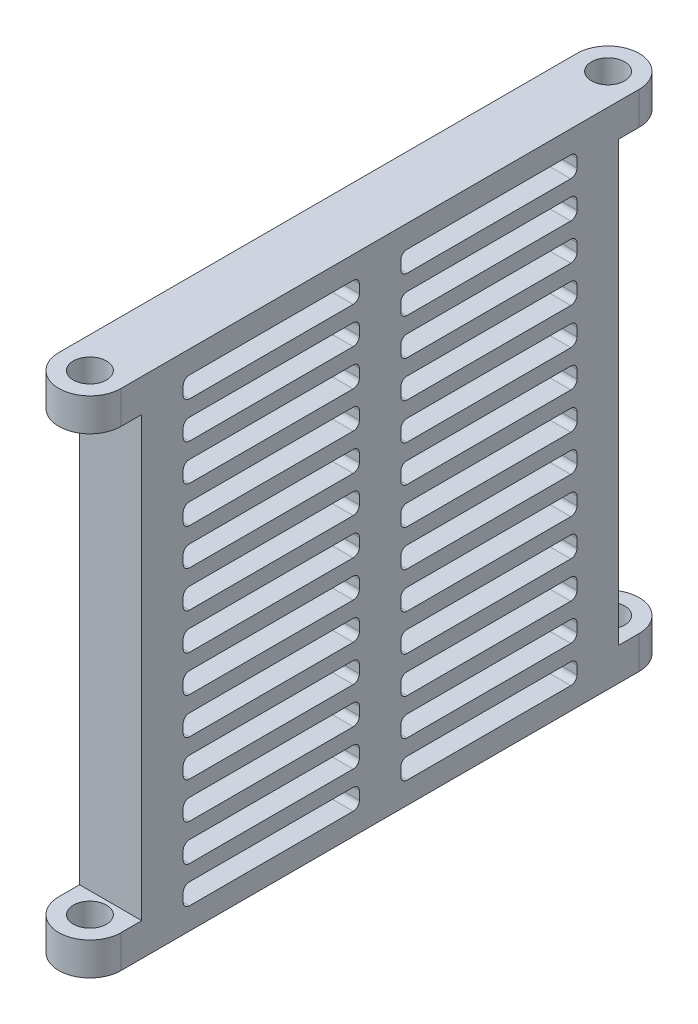
SolidWorks part; units mm, degrees
ref_plane "Front Plane" through (0, 0, 0) normal (0, 0, 1) x (1, 0, 0)
ref_plane "Top Plane" through (0, 0, 0) normal (0, 1, 0) x (1, 0, 0)
ref_plane "Right Plane" through (0, 0, 0) normal (1, 0, 0) x (0, 0, -1)
sketch "Sketch2" plane through (0, 0, 0) normal (0, 1, 0) x (1, 0, 0)
  line L0 (-3, 0) -> (-3, -50)
  line L1 (3, -50) -> (3, 0)
  arc A0 (3, 0) -> (-3, 0) centre (0, 0) ccw
  arc A1 (-3, -50) -> (3, -50) centre (0, -50) ccw
  circle A2 centre (0, 0) radius 1.6
  circle A3 centre (0, -50) radius 1.6
  dimension "D1" = 3.2
  dimension "D2" = 3
  dimension "D3" = 50
extrude "Boss-Extrude1" add sketch "Sketch2" along normal blind 3.175
sketch "Sketch3" plane through (0, 3.175, 0) normal (0, 1, 0) x (1, 0, 0)
  line L0 (-3, 0) -> (-3, -50) construction
  line L1 (-3, -2) -> (3, -2)
  line L2 (-3, -2) -> (-3, -48)
  line L3 (-3, -48) -> (3, -48)
  line L4 (3, -2) -> (3, -48)
  line L5 (3, -50) -> (3, 0) construction
  circle A0 centre (0, -50) radius 1.6 construction
  point P9 (0, -48)
  dimension "D1" = 2
  dimension "D2" = 2
extrude "Boss-Extrude2" add sketch "Sketch3" along normal blind 42.3
ref_plane "Plane1" through (0, 24.325, 0) normal (0, 1, 0) x (1, 0, 0)
mirror "Mirror2" about plane through (0, 24.325, 0) normal (0, 1, 0) of "Boss-Extrude1"
sketch "Sketch4" plane through (3, 0, 0) normal (1, 0, 0) x (0, 0, -1)
  line L0 (-2, 45.475) -> (-48, 45.475) construction
  line L3 (-2, 3.175) -> (-48, 3.175) construction
  line L11 (-25, 48.65) -> (-25, 0) construction
  line L12 (-50, 48.65) -> (0, 48.65) construction
  line L24 (-50, 0) -> (0, 0) construction
  line L25 (-2, 45.475) -> (-2, 3.175) construction
  line L30 (-6.6, 46.475) -> (-22.4, 46.475)
  line L39 (-6, 45.875) -> (-6, 45.075)
  line L40 (-6.6, 44.475) -> (-22.4, 44.475)
  line L41 (-23, 45.875) -> (-23, 45.075)
  line L46 (-6, 46.475) -> (-23, 44.475) construction
  line L47 (-6, 44.475) -> (-23, 46.475) construction
  line L64 (-6.6, 42.945) -> (-22.4, 42.945)
  line L69 (-6, 42.345) -> (-6, 41.545)
  line L70 (-6.6, 40.945) -> (-22.4, 40.945)
  line L71 (-23, 42.345) -> (-23, 41.545)
  line L72 (-2, 41.945) -> (-48, 41.945) construction
  line L73 (-6, 42.945) -> (-23, 40.945) construction
  line L74 (-6, 40.945) -> (-23, 42.945) construction
  line L75 (-6.6, 39.415) -> (-22.4, 39.415)
  line L76 (-6, 38.815) -> (-6, 38.015)
  line L77 (-6.6, 37.415) -> (-22.4, 37.415)
  line L78 (-23, 38.815) -> (-23, 38.015)
  line L79 (-2, 38.415) -> (-48, 38.415) construction
  line L132 (-6, 39.415) -> (-23, 37.415) construction
  line L133 (-6, 37.415) -> (-23, 39.415) construction
  line L134 (-6.6, 35.885) -> (-22.4, 35.885)
  line L135 (-6, 35.285) -> (-6, 34.485)
  line L136 (-6.6, 33.885) -> (-22.4, 33.885)
  line L137 (-23, 35.285) -> (-23, 34.485)
  line L138 (-2, 34.885) -> (-48, 34.885) construction
  line L139 (-6, 35.885) -> (-23, 33.885) construction
  line L140 (-6, 33.885) -> (-23, 35.885) construction
  line L141 (-6.6, 32.355) -> (-22.4, 32.355)
  line L142 (-6, 31.755) -> (-6, 30.955)
  line L143 (-6.6, 30.355) -> (-22.4, 30.355)
  line L144 (-23, 31.755) -> (-23, 30.955)
  line L145 (-2, 31.355) -> (-48, 31.355) construction
  line L146 (-6, 32.355) -> (-23, 30.355) construction
  line L147 (-6, 30.355) -> (-23, 32.355) construction
  line L148 (-6.6, 28.825) -> (-22.4, 28.825)
  line L149 (-6, 28.225) -> (-6, 27.425)
  line L201 (-6.6, 26.825) -> (-22.4, 26.825)
  line L202 (-23, 28.225) -> (-23, 27.425)
  line L203 (-2, 27.825) -> (-48, 27.825) construction
  line L204 (-6, 28.825) -> (-23, 26.825) construction
  line L205 (-6, 26.825) -> (-23, 28.825) construction
  line L206 (-6.6, 25.295) -> (-22.4, 25.295)
  line L207 (-6, 24.695) -> (-6, 23.895)
  line L208 (-6.6, 23.295) -> (-22.4, 23.295)
  line L209 (-23, 24.695) -> (-23, 23.895)
  line L210 (-2, 24.295) -> (-48, 24.295) construction
  line L211 (-6, 25.295) -> (-23, 23.295) construction
  line L212 (-6, 23.295) -> (-23, 25.295) construction
  line L213 (-6.6, 21.765) -> (-22.4, 21.765)
  line L214 (-6, 21.165) -> (-6, 20.365)
  line L215 (-6.6, 19.765) -> (-22.4, 19.765)
  line L216 (-23, 21.165) -> (-23, 20.365)
  line L217 (-2, 20.765) -> (-48, 20.765) construction
  line L218 (-6, 21.765) -> (-23, 19.765) construction
  line L219 (-6, 19.765) -> (-23, 21.765) construction
  line L220 (-6.6, 18.235) -> (-22.4, 18.235)
  line L221 (-6, 17.635) -> (-6, 16.835)
  line L222 (-6.6, 16.235) -> (-22.4, 16.235)
  line L223 (-23, 17.635) -> (-23, 16.835)
  line L224 (-2, 17.235) -> (-48, 17.235) construction
  line L225 (-6, 18.235) -> (-23, 16.235) construction
  line L226 (-6, 16.235) -> (-23, 18.235) construction
  line L227 (-6.6, 14.705) -> (-22.4, 14.705)
  line L228 (-6, 14.105) -> (-6, 13.305)
  line L229 (-6.6, 12.705) -> (-22.4, 12.705)
  line L230 (-23, 14.105) -> (-23, 13.305)
  line L231 (-2, 13.705) -> (-48, 13.705) construction
  line L232 (-6, 14.705) -> (-23, 12.705) construction
  line L233 (-6, 12.705) -> (-23, 14.705) construction
  line L234 (-6.6, 11.175) -> (-22.4, 11.175)
  line L235 (-6, 10.575) -> (-6, 9.775)
  line L236 (-6.6, 9.175) -> (-22.4, 9.175)
  line L237 (-23, 10.575) -> (-23, 9.775)
  line L238 (-2, 10.175) -> (-48, 10.175) construction
  line L239 (-6, 11.175) -> (-23, 9.175) construction
  line L240 (-6, 9.175) -> (-23, 11.175) construction
  line L241 (-6.6, 7.645) -> (-22.4, 7.645)
  line L242 (-6, 7.045) -> (-6, 6.245)
  line L243 (-6.6, 5.645) -> (-22.4, 5.645)
  line L244 (-23, 7.045) -> (-23, 6.245)
  line L245 (-2, 6.645) -> (-48, 6.645) construction
  line L246 (-6, 7.645) -> (-23, 5.645) construction
  line L247 (-6, 5.645) -> (-23, 7.645) construction
  line L248 (-6.6, 4.115) -> (-22.4, 4.115)
  line L249 (-6, 3.515) -> (-6, 2.715)
  line L250 (-6.6, 2.115) -> (-22.4, 2.115)
  line L251 (-23, 3.515) -> (-23, 2.715)
  line L252 (-2, 3.115) -> (-48, 3.115) construction
  line L253 (-6, 4.115) -> (-23, 2.115) construction
  line L254 (-6, 2.115) -> (-23, 4.115) construction
  line L255 (-44, 2.115) -> (-27, 4.115) construction
  line L256 (-44, 4.115) -> (-27, 2.115) construction
  line L257 (-44, 5.645) -> (-27, 7.645) construction
  line L258 (-44, 7.645) -> (-27, 5.645) construction
  line L259 (-44, 9.175) -> (-27, 11.175) construction
  line L260 (-44, 11.175) -> (-27, 9.175) construction
  line L261 (-44, 12.705) -> (-27, 14.705) construction
  line L262 (-44, 14.705) -> (-27, 12.705) construction
  line L263 (-44, 16.235) -> (-27, 18.235) construction
  line L264 (-44, 18.235) -> (-27, 16.235) construction
  line L265 (-44, 19.765) -> (-27, 21.765) construction
  line L266 (-44, 21.765) -> (-27, 19.765) construction
  line L267 (-44, 23.295) -> (-27, 25.295) construction
  line L268 (-44, 25.295) -> (-27, 23.295) construction
  line L269 (-44, 26.825) -> (-27, 28.825) construction
  line L270 (-44, 28.825) -> (-27, 26.825) construction
  line L271 (-44, 30.355) -> (-27, 32.355) construction
  line L272 (-44, 32.355) -> (-27, 30.355) construction
  line L273 (-44, 33.885) -> (-27, 35.885) construction
  line L274 (-44, 35.885) -> (-27, 33.885) construction
  line L275 (-44, 37.415) -> (-27, 39.415) construction
  line L276 (-44, 39.415) -> (-27, 37.415) construction
  line L277 (-44, 40.945) -> (-27, 42.945) construction
  line L278 (-44, 42.945) -> (-27, 40.945) construction
  line L279 (-44, 44.475) -> (-27, 46.475) construction
  line L280 (-44, 46.475) -> (-27, 44.475) construction
  line L281 (-27, 3.515) -> (-27, 2.715)
  line L282 (-43.4, 2.115) -> (-27.6, 2.115)
  line L283 (-44, 3.515) -> (-44, 2.715)
  line L284 (-43.4, 4.115) -> (-27.6, 4.115)
  line L285 (-27, 7.045) -> (-27, 6.245)
  line L286 (-43.4, 5.645) -> (-27.6, 5.645)
  line L287 (-44, 7.045) -> (-44, 6.245)
  line L288 (-43.4, 7.645) -> (-27.6, 7.645)
  line L289 (-27, 10.575) -> (-27, 9.775)
  line L290 (-43.4, 9.175) -> (-27.6, 9.175)
  line L291 (-44, 10.575) -> (-44, 9.775)
  line L292 (-43.4, 11.175) -> (-27.6, 11.175)
  line L293 (-27, 14.105) -> (-27, 13.305)
  line L294 (-43.4, 12.705) -> (-27.6, 12.705)
  line L295 (-44, 14.105) -> (-44, 13.305)
  line L296 (-43.4, 14.705) -> (-27.6, 14.705)
  line L297 (-27, 17.635) -> (-27, 16.835)
  line L298 (-43.4, 16.235) -> (-27.6, 16.235)
  line L299 (-44, 17.635) -> (-44, 16.835)
  line L300 (-43.4, 18.235) -> (-27.6, 18.235)
  line L301 (-27, 21.165) -> (-27, 20.365)
  line L302 (-43.4, 19.765) -> (-27.6, 19.765)
  line L303 (-44, 21.165) -> (-44, 20.365)
  line L304 (-43.4, 21.765) -> (-27.6, 21.765)
  line L305 (-27, 24.695) -> (-27, 23.895)
  line L306 (-43.4, 23.295) -> (-27.6, 23.295)
  line L307 (-44, 24.695) -> (-44, 23.895)
  line L308 (-43.4, 25.295) -> (-27.6, 25.295)
  line L309 (-27, 28.225) -> (-27, 27.425)
  line L310 (-43.4, 26.825) -> (-27.6, 26.825)
  line L311 (-44, 28.225) -> (-44, 27.425)
  line L312 (-43.4, 28.825) -> (-27.6, 28.825)
  line L313 (-27, 31.755) -> (-27, 30.955)
  line L314 (-43.4, 30.355) -> (-27.6, 30.355)
  line L315 (-44, 31.755) -> (-44, 30.955)
  line L316 (-43.4, 32.355) -> (-27.6, 32.355)
  line L317 (-27, 35.285) -> (-27, 34.485)
  line L318 (-43.4, 33.885) -> (-27.6, 33.885)
  line L319 (-44, 35.285) -> (-44, 34.485)
  line L320 (-43.4, 35.885) -> (-27.6, 35.885)
  line L321 (-27, 38.815) -> (-27, 38.015)
  line L322 (-43.4, 37.415) -> (-27.6, 37.415)
  line L323 (-44, 38.815) -> (-44, 38.015)
  line L324 (-43.4, 39.415) -> (-27.6, 39.415)
  line L325 (-27, 42.345) -> (-27, 41.545)
  line L326 (-43.4, 40.945) -> (-27.6, 40.945)
  line L327 (-44, 42.345) -> (-44, 41.545)
  line L328 (-43.4, 42.945) -> (-27.6, 42.945)
  line L329 (-27, 45.875) -> (-27, 45.075)
  line L330 (-43.4, 44.475) -> (-27.6, 44.475)
  line L331 (-44, 45.875) -> (-44, 45.075)
  line L332 (-43.4, 46.475) -> (-27.6, 46.475)
  arc A76 (-22.4, 46.475) -> (-23, 45.875) centre (-22.4, 45.875) ccw
  arc A77 (-22.4, 44.475) -> (-23, 45.075) centre (-22.4, 45.075) cw
  arc A78 (-6.6, 46.475) -> (-6, 45.875) centre (-6.6, 45.875) cw
  arc A79 (-6, 45.075) -> (-6.6, 44.475) centre (-6.6, 45.075) cw
  arc A80 (-22.4, 42.945) -> (-23, 42.345) centre (-22.4, 42.345) ccw
  arc A81 (-22.4, 40.945) -> (-23, 41.545) centre (-22.4, 41.545) cw
  arc A82 (-6.6, 42.945) -> (-6, 42.345) centre (-6.6, 42.345) cw
  arc A83 (-6, 41.545) -> (-6.6, 40.945) centre (-6.6, 41.545) cw
  arc A84 (-22.4, 39.415) -> (-23, 38.815) centre (-22.4, 38.815) ccw
  arc A85 (-22.4, 37.415) -> (-23, 38.015) centre (-22.4, 38.015) cw
  arc A86 (-6.6, 39.415) -> (-6, 38.815) centre (-6.6, 38.815) cw
  arc A87 (-6, 38.015) -> (-6.6, 37.415) centre (-6.6, 38.015) cw
  arc A88 (-22.4, 35.885) -> (-23, 35.285) centre (-22.4, 35.285) ccw
  arc A89 (-22.4, 33.885) -> (-23, 34.485) centre (-22.4, 34.485) cw
  arc A90 (-6.6, 35.885) -> (-6, 35.285) centre (-6.6, 35.285) cw
  arc A91 (-6, 34.485) -> (-6.6, 33.885) centre (-6.6, 34.485) cw
  arc A92 (-22.4, 32.355) -> (-23, 31.755) centre (-22.4, 31.755) ccw
  arc A93 (-22.4, 30.355) -> (-23, 30.955) centre (-22.4, 30.955) cw
  arc A94 (-6.6, 32.355) -> (-6, 31.755) centre (-6.6, 31.755) cw
  arc A95 (-6, 30.955) -> (-6.6, 30.355) centre (-6.6, 30.955) cw
  arc A96 (-22.4, 28.825) -> (-23, 28.225) centre (-22.4, 28.225) ccw
  arc A97 (-22.4, 26.825) -> (-23, 27.425) centre (-22.4, 27.425) cw
  arc A98 (-6.6, 28.825) -> (-6, 28.225) centre (-6.6, 28.225) cw
  arc A99 (-6, 27.425) -> (-6.6, 26.825) centre (-6.6, 27.425) cw
  arc A100 (-22.4, 25.295) -> (-23, 24.695) centre (-22.4, 24.695) ccw
  arc A101 (-22.4, 23.295) -> (-23, 23.895) centre (-22.4, 23.895) cw
  arc A102 (-6.6, 25.295) -> (-6, 24.695) centre (-6.6, 24.695) cw
  arc A103 (-6, 23.895) -> (-6.6, 23.295) centre (-6.6, 23.895) cw
  arc A104 (-22.4, 21.765) -> (-23, 21.165) centre (-22.4, 21.165) ccw
  arc A105 (-22.4, 19.765) -> (-23, 20.365) centre (-22.4, 20.365) cw
  arc A106 (-6.6, 21.765) -> (-6, 21.165) centre (-6.6, 21.165) cw
  arc A107 (-6, 20.365) -> (-6.6, 19.765) centre (-6.6, 20.365) cw
  arc A108 (-22.4, 18.235) -> (-23, 17.635) centre (-22.4, 17.635) ccw
  arc A109 (-22.4, 16.235) -> (-23, 16.835) centre (-22.4, 16.835) cw
  arc A110 (-6.6, 18.235) -> (-6, 17.635) centre (-6.6, 17.635) cw
  arc A111 (-6, 16.835) -> (-6.6, 16.235) centre (-6.6, 16.835) cw
  arc A112 (-22.4, 14.705) -> (-23, 14.105) centre (-22.4, 14.105) ccw
  arc A113 (-22.4, 12.705) -> (-23, 13.305) centre (-22.4, 13.305) cw
  arc A114 (-6.6, 14.705) -> (-6, 14.105) centre (-6.6, 14.105) cw
  arc A115 (-6, 13.305) -> (-6.6, 12.705) centre (-6.6, 13.305) cw
  arc A116 (-22.4, 11.175) -> (-23, 10.575) centre (-22.4, 10.575) ccw
  arc A117 (-22.4, 9.175) -> (-23, 9.775) centre (-22.4, 9.775) cw
  arc A118 (-6.6, 11.175) -> (-6, 10.575) centre (-6.6, 10.575) cw
  arc A119 (-6, 9.775) -> (-6.6, 9.175) centre (-6.6, 9.775) cw
  arc A120 (-22.4, 7.645) -> (-23, 7.045) centre (-22.4, 7.045) ccw
  arc A121 (-22.4, 5.645) -> (-23, 6.245) centre (-22.4, 6.245) cw
  arc A122 (-6.6, 7.645) -> (-6, 7.045) centre (-6.6, 7.045) cw
  arc A123 (-6, 6.245) -> (-6.6, 5.645) centre (-6.6, 6.245) cw
  arc A124 (-22.4, 4.115) -> (-23, 3.515) centre (-22.4, 3.515) ccw
  arc A125 (-22.4, 2.115) -> (-23, 2.715) centre (-22.4, 2.715) cw
  arc A126 (-6.6, 4.115) -> (-6, 3.515) centre (-6.6, 3.515) cw
  arc A127 (-6, 2.715) -> (-6.6, 2.115) centre (-6.6, 2.715) cw
  arc A128 (-44, 2.715) -> (-43.4, 2.115) centre (-43.4, 2.715) ccw
  arc A129 (-43.4, 4.115) -> (-44, 3.515) centre (-43.4, 3.515) ccw
  arc A130 (-27.6, 2.115) -> (-27, 2.715) centre (-27.6, 2.715) ccw
  arc A131 (-27.6, 4.115) -> (-27, 3.515) centre (-27.6, 3.515) cw
  arc A132 (-44, 6.245) -> (-43.4, 5.645) centre (-43.4, 6.245) ccw
  arc A133 (-43.4, 7.645) -> (-44, 7.045) centre (-43.4, 7.045) ccw
  arc A134 (-27.6, 5.645) -> (-27, 6.245) centre (-27.6, 6.245) ccw
  arc A135 (-27.6, 7.645) -> (-27, 7.045) centre (-27.6, 7.045) cw
  arc A136 (-44, 9.775) -> (-43.4, 9.175) centre (-43.4, 9.775) ccw
  arc A137 (-43.4, 11.175) -> (-44, 10.575) centre (-43.4, 10.575) ccw
  arc A138 (-27.6, 9.175) -> (-27, 9.775) centre (-27.6, 9.775) ccw
  arc A139 (-27.6, 11.175) -> (-27, 10.575) centre (-27.6, 10.575) cw
  arc A140 (-44, 13.305) -> (-43.4, 12.705) centre (-43.4, 13.305) ccw
  arc A141 (-43.4, 14.705) -> (-44, 14.105) centre (-43.4, 14.105) ccw
  arc A142 (-27.6, 12.705) -> (-27, 13.305) centre (-27.6, 13.305) ccw
  arc A143 (-27.6, 14.705) -> (-27, 14.105) centre (-27.6, 14.105) cw
  arc A144 (-44, 16.835) -> (-43.4, 16.235) centre (-43.4, 16.835) ccw
  arc A145 (-43.4, 18.235) -> (-44, 17.635) centre (-43.4, 17.635) ccw
  arc A146 (-27.6, 16.235) -> (-27, 16.835) centre (-27.6, 16.835) ccw
  arc A147 (-27.6, 18.235) -> (-27, 17.635) centre (-27.6, 17.635) cw
  arc A148 (-44, 20.365) -> (-43.4, 19.765) centre (-43.4, 20.365) ccw
  arc A149 (-43.4, 21.765) -> (-44, 21.165) centre (-43.4, 21.165) ccw
  arc A150 (-27.6, 19.765) -> (-27, 20.365) centre (-27.6, 20.365) ccw
  arc A151 (-27.6, 21.765) -> (-27, 21.165) centre (-27.6, 21.165) cw
  arc A152 (-44, 23.895) -> (-43.4, 23.295) centre (-43.4, 23.895) ccw
  arc A153 (-43.4, 25.295) -> (-44, 24.695) centre (-43.4, 24.695) ccw
  arc A154 (-27.6, 23.295) -> (-27, 23.895) centre (-27.6, 23.895) ccw
  arc A155 (-27.6, 25.295) -> (-27, 24.695) centre (-27.6, 24.695) cw
  arc A156 (-44, 27.425) -> (-43.4, 26.825) centre (-43.4, 27.425) ccw
  arc A157 (-43.4, 28.825) -> (-44, 28.225) centre (-43.4, 28.225) ccw
  arc A158 (-27.6, 26.825) -> (-27, 27.425) centre (-27.6, 27.425) ccw
  arc A159 (-27.6, 28.825) -> (-27, 28.225) centre (-27.6, 28.225) cw
  arc A160 (-44, 30.955) -> (-43.4, 30.355) centre (-43.4, 30.955) ccw
  arc A161 (-43.4, 32.355) -> (-44, 31.755) centre (-43.4, 31.755) ccw
  arc A162 (-27.6, 30.355) -> (-27, 30.955) centre (-27.6, 30.955) ccw
  arc A163 (-27.6, 32.355) -> (-27, 31.755) centre (-27.6, 31.755) cw
  arc A164 (-44, 34.485) -> (-43.4, 33.885) centre (-43.4, 34.485) ccw
  arc A165 (-43.4, 35.885) -> (-44, 35.285) centre (-43.4, 35.285) ccw
  arc A166 (-27.6, 33.885) -> (-27, 34.485) centre (-27.6, 34.485) ccw
  arc A167 (-27.6, 35.885) -> (-27, 35.285) centre (-27.6, 35.285) cw
  arc A168 (-44, 38.015) -> (-43.4, 37.415) centre (-43.4, 38.015) ccw
  arc A169 (-43.4, 39.415) -> (-44, 38.815) centre (-43.4, 38.815) ccw
  arc A170 (-27.6, 37.415) -> (-27, 38.015) centre (-27.6, 38.015) ccw
  arc A171 (-27.6, 39.415) -> (-27, 38.815) centre (-27.6, 38.815) cw
  arc A172 (-44, 41.545) -> (-43.4, 40.945) centre (-43.4, 41.545) ccw
  arc A173 (-43.4, 42.945) -> (-44, 42.345) centre (-43.4, 42.345) ccw
  arc A174 (-27.6, 40.945) -> (-27, 41.545) centre (-27.6, 41.545) ccw
  arc A175 (-27.6, 42.945) -> (-27, 42.345) centre (-27.6, 42.345) cw
  arc A176 (-44, 45.075) -> (-43.4, 44.475) centre (-43.4, 45.075) ccw
  arc A177 (-43.4, 46.475) -> (-44, 45.875) centre (-43.4, 45.875) ccw
  arc A178 (-27.6, 44.475) -> (-27, 45.075) centre (-27.6, 45.075) ccw
  arc A179 (-27.6, 46.475) -> (-27, 45.875) centre (-27.6, 45.875) cw
  point P10 (-14.5, 45.475)
  point P13 (-14.25, 34.325)
  point P14 (-14.25, 31.825)
  point P15 (-14.25, 29.325)
  point P16 (-14.25, 26.825)
  point P36 (-14.5, 41.945)
  point P55 (-14.5, 38.415)
  point P74 (-14.5, 34.885)
  point P93 (-14.5, 31.355)
  point P112 (-14.5, 27.825)
  point P131 (-14.5, 24.295)
  point P150 (-14.5, 20.765)
  point P169 (-14.5, 17.235)
  point P188 (-14.5, 13.705)
  point P207 (-14.5, 10.175)
  point P226 (-14.5, 6.645)
  point P245 (-14.5, 3.115)
  point P515 (-35.5, 3.115)
  point P516 (-35.5, 6.645)
  point P517 (-35.5, 10.175)
  point P518 (-35.5, 13.705)
  point P519 (-35.5, 17.235)
  point P520 (-35.5, 20.765)
  point P521 (-35.5, 24.295)
  point P522 (-35.5, 27.825)
  point P523 (-35.5, 31.355)
  point P524 (-35.5, 34.885)
  point P525 (-35.5, 38.415)
  point P526 (-35.5, 41.945)
  point P527 (-35.5, 45.475)
  dimension "D6" = 1.53
  dimension "D4" = 0.6
  dimension "D1" = 2
  dimension "D2" = 4
  dimension "D3" = 2
  dimension "D5" = 13
extrude "Cut-Extrude1" cut sketch "Sketch4" against normal through all
equation "\"D2@Sketch3\"=\"D1@Sketch3\""
